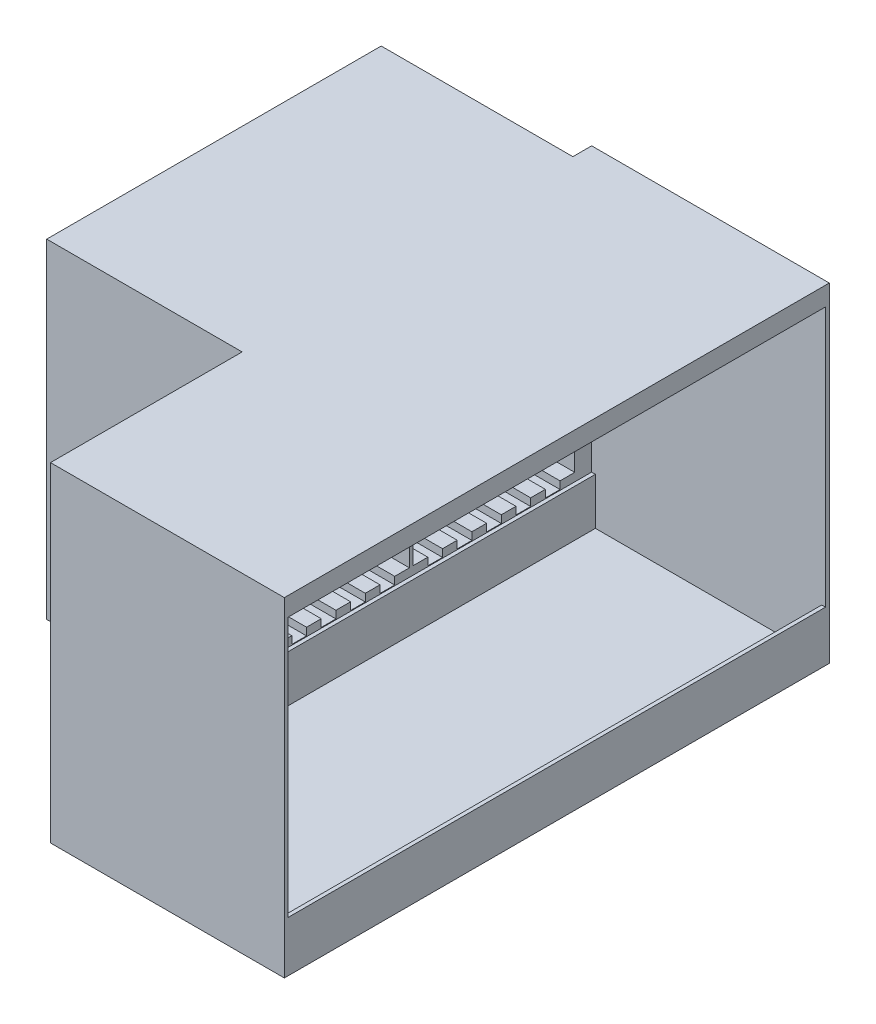
SolidWorks part; units mm, degrees
other "Исправление1"
sketch "Эскиз13" plane through (1050, -360, 1224.5) normal (0.916, -0.3443, 0.206) x (0.3981, 0.8438, -0.36)
ref_plane "Спереди" through (0, 0, 0) normal (0, 0, 1) x (1, 0, 0)
ref_plane "Сверху" through (0, 0, 0) normal (0, 1, 0) x (1, 0, 0)
ref_plane "Справа" through (0, 0, 0) normal (1, 0, 0) x (0, 0, -1)
other "Configuration Table"
sketch "Основа эскиз" plane through (0, 0, 0) normal (1, 0, 0) x (0, 0, -1)
  line L1 (-470, 438.28) -> (470, 438.28)
  line L2 (-470, 438.28) -> (-470, -438.28)
  line L3 (-470, -438.28) -> (470, -438.28)
  line L4 (470, 438.28) -> (470, -438.28)
  point P4 (0, 438.28)
  point P8 (-470, 0)
  dimension "D2" = 940
  dimension "D1" = 876.56
extrude "Основа" add sketch "Основа эскиз" along normal blind 1142.3
sketch "Вырез коретки эскиз" plane through (1142.3, 0, 0) normal (1, 0, 0) x (0, 0, -1)
  line L5 (470, 438.28) -> (-470, 438.28) construction
  line L6 (-470, 388.28) -> (460, 388.28)
  line L7 (-470, -438.28) -> (470, -438.28) construction
  line L8 (-470, 388.28) -> (-470, -303.68)
  line L9 (-470, -303.68) -> (460, -303.68)
  line L10 (460, 388.28) -> (460, -303.68)
  line L11 (-470, 438.28) -> (-470, -438.28) construction
  line L12 (470, -438.28) -> (470, 438.28) construction
  point P0 (0, 0)
  dimension "D3" = 10
  dimension "D4" = 134.6
extrude "Вырез коретки" cut sketch "Вырез коретки эскиз" against normal blind 622.3
sketch "вырез ячейки эскиз" plane through (520, 0, 0) normal (1, 0, 0) x (0, 0, -1)
  line L0 (460, 388.28) -> (-470, 388.28) construction
  line L1 (-455, 388.28) -> (-25, 388.28)
  line L2 (-455, 388.28) -> (-455, 68.28)
  line L3 (-455, 68.28) -> (-25, 68.28)
  line L4 (-25, 388.28) -> (-25, 68.28)
  line L17 (-470, 388.28) -> (-470, -303.68) construction
  dimension "D7" = 430
  dimension "D8" = 320
  dimension "D1" = 15
extrude "вырез ячейки" cut sketch "вырез ячейки эскиз" against normal blind 510
sketch "вырез двери эскиз" plane through (0, 0, 0) normal (-1, 0, 0) x (0, 0, 1)
  line L1 (25, 388.28) -> (460, 388.28)
  line L2 (25, 388.28) -> (25, 68.28)
  line L3 (25, 68.28) -> (460, 68.28)
  line L4 (460, 388.28) -> (460, 68.28)
  line L6 (455, 68.28) -> (25, 68.28) construction
  line L7 (25, 68.28) -> (25, 388.28) construction
  line L8 (455, 388.28) -> (455, 68.28) construction
  line L9 (455, 388.28) -> (455, 68.28) construction
  line L10 (25, 388.28) -> (455, 388.28) construction
  dimension "D2" = 5
extrude "вырез двери" cut sketch "вырез двери эскиз" against normal blind 10
sketch "Вырез основание низ эскиз" plane through (0, -303.68, 0) normal (0, 1, 0) x (1, 0, 0)
  line L0 (1142.3, -470) -> (1142.3, 460) construction
  line L1 (530, 460) -> (1132.3, 460)
  line L2 (530, 460) -> (530, -470)
  line L3 (530, -470) -> (1132.3, -470)
  line L4 (1132.3, 460) -> (1132.3, -470)
  line L5 (520, 460) -> (1142.3, 460) construction
  line L6 (520, -470) -> (1142.3, -470) construction
  dimension "D1" = 10
  dimension "D2" = 602.3
extrude "Вырез основание низ" cut sketch "Вырез основание низ эскиз" against normal blind 124.6
sketch "Вырез основания верх эскиз" plane through (0, 388.28, 0) normal (0, -1, 0) x (1, 0, 0)
  line L0 (520, 470) -> (1142.3, 470) construction
  line L1 (530, -460) -> (1132.3, -460)
  line L2 (530, -460) -> (530, 470)
  line L3 (530, 470) -> (1132.3, 470)
  line L4 (1132.3, -460) -> (1132.3, 470)
  line L5 (520, -460) -> (1142.3, -460) construction
  line L6 (1142.3, -460) -> (1142.3, 470) construction
  dimension "D1" = 10
  dimension "D2" = 602.3
extrude "Вырез основание верх" cut sketch "Вырез основания верх эскиз" against normal blind 40
sketch "вырез полозья эскиз" plane through (520, 0, 0) normal (1, 0, 0) x (0, 0, -1)
  line L0 (-455, 68.28) -> (-25, 68.28) construction
  line L1 (-415.9091, 68.28) -> (-376.8182, 68.28)
  line L2 (-415.9091, 68.28) -> (-415.9091, 48.28)
  line L3 (-415.9091, 48.28) -> (-376.8182, 48.28)
  line L4 (-376.8182, 68.28) -> (-376.8182, 48.28)
  dimension "D2" = 39.0909
  dimension "D3" = 39.0909
extrude "Вырез полозья" cut sketch "вырез полозья эскиз" against normal blind 510
pattern_linear "Линейный массив полозьев" count 5 spacing 78.1818 along (0, 0, -1) of "Вырез полозья"
pattern_linear "Линейный массив ячеек" count 2 spacing 440 along (0, 0, -1) count 2 spacing 350 along (0, -1, 0) of "Линейный массив полозьев", "вырез двери", "вырез ячейки"
sketch "Основание эскиз" plane through (0, 0, 470) normal (0, 0, 1) x (1, 0, 0)
  line L0 (1142.3, -438.28) -> (1142.3, -303.68)
  line L1 (1142.3, -303.68) -> (1132.3, -303.68)
  line L2 (1132.3, -303.68) -> (1132.3, -428.28)
  line L3 (1132.3, -428.28) -> (530, -428.28)
  line L4 (530, -428.28) -> (530, -303.68)
  line L5 (530, -303.68) -> (520, -303.68)
  line L6 (520, -303.68) -> (520, -438.28)
  line L7 (1142.3, -438.28) -> (0, -438.28) construction
  line L8 (520, -438.28) -> (1142.3, -438.28)
  line L9 (1132.3, 388.28) -> (1142.3, 388.28)
  line L10 (1142.3, 388.28) -> (1142.3, 438.28)
  line L11 (1142.3, 438.28) -> (520, 438.28)
  line L12 (1142.3, 438.28) -> (0, 438.28) construction
  line L13 (520, 438.28) -> (520, 388.28)
  line L14 (520, 388.28) -> (530, 388.28)
  line L15 (530, 388.28) -> (530, 428.28)
  line L16 (530, 428.28) -> (1132.3, 428.28)
  line L17 (1132.3, 428.28) -> (1132.3, 388.28)
extrude "Основание" add sketch "Основание эскиз" along normal blind 500
sketch "Стенка боквая эскиз" plane through (0, 0, 970) normal (0, 0, 1) x (1, 0, 0)
  line L1 (1142.3, 438.28) -> (520, 438.28)
  line L2 (1142.3, 438.28) -> (1142.3, -438.28)
  line L3 (1142.3, -438.28) -> (520, -438.28)
  line L4 (520, 438.28) -> (520, -438.28)
extrude "Стенка боковая" add sketch "Стенка боквая эскиз" along normal blind 10
sketch "Эскиз14" plane through (0, 0, -470) normal (0, 0, -1) x (-1, 0, 0)
  line L0 (-1142.3, 438.28) -> (0, 438.28) construction
  line L1 (0, -438.28) -> (-510, -438.28)
  line L2 (0, -438.28) -> (0, 438.28)
  line L3 (0, 438.28) -> (-510, 438.28)
  line L4 (-510, -438.28) -> (-510, 438.28)
  dimension "D1" = 510
extrude "Вырез-Вытянуть1" cut sketch "Эскиз14" against normal blind 50
equation "\"Ширина груза\"= 420"
equation "\"Глубина груза\"= 490"
equation "\"Высота груза\"= 297"
equation "\"Ширина ячейки\"= \"Ширина груза\" + 10"
equation "\"Глубина ячейки\"= \"Глубина груза\" + 10"
equation "\"Высота ячейки\"= \"Высота груза\" + 10 + 13"
equation "\"Колво ячеек ширина\"= 2"
equation "\"Колво ячеек высота\"= 2"
equation "\"Толщина стенки\"= 10"
equation "\"D2@Основа эскиз\"=( \"Ширина ячейки\" + \"Толщина стенки\" + \"Крепление дверцы\" ) * \"Колво ячеек ширина\" + \"Ширина пластины\""
equation "\"D1@Основа эскиз\"=( \"Высота ячейки\" + \"Толщина стенки\" + \"Высота пола\" ) * \"Колво ячеек высота\" + \"Отступ рейки\" * 2 + \"Высота рейки\" * 2 + \"Толщина стенки\" * 2 + \"Мотор X ширина корпуса\" + \"Мотор Y ширина корпуса\"- 8.04"
equation "\"Крепление дверцы\"= 5"
equation "\"D7@вырез ячейки эскиз\"= \"Ширина ячейки\""
equation "\"D1@вырез ячейки эскиз\" = \"Толщина стенки\" + \"Крепление дверцы\""
equation "\"D8@вырез ячейки эскиз\"= \"Высота ячейки\""
equation "\"D2@вырез двери эскиз\"= \"Крепление дверцы\""
equation "\"D1@Основа\"=\"Глубина ячейки\" + \"Глубина каретки\" + \"Толщина стенки\" * 4 + \"Ширина рейки\" "
equation "\"D1@Вырез коретки\"=\"Глубина каретки\" + \"Толщина стенки\" * 2 + \"Ширина рейки\""
equation "\"D1@Вырез основание низ эскиз\"=\"Толщина стенки\" "
equation "\"Ширина рейки\"= \"Толщина шестерни\""
equation "\"D1@вырез ячейки\"= \"Глубина ячейки\" + \"Толщина стенки\""
equation "\"D1@вырез двери\"= \"Толщина стенки\""
equation "\"D2@Вырез основание низ эскиз\"=\"Глубина каретки\" + \"Ширина рейки\""
equation "\"Высота рейки\"= 20"
equation "\"D1@Вырез основания верх эскиз\"=\"Толщина стенки\""
equation "\"D2@Вырез основания верх эскиз\"=\"Глубина каретки\" + \"Ширина рейки\" "
equation "\"D1@Вырез основание верх\" = \"Высота рейки\" + \"Отступ рейки\""
equation "\"D4@Вырез коретки эскиз\"=\"Толщина стенки\"  + \"Высота рейки\" + \"Отступ рейки\" + \"Мотор X ширина корпуса\" + \"Мотор Y ширина корпуса\""
equation "\"D1@Вырез коретки эскиз\"=\"Толщина стенки\" + \"Высота рейки\" + \"Отступ рейки\" "
equation "\"D3@Вырез коретки эскиз\" = \"Толщина стенки\""
equation "\"D1@Вырез основание низ\"=\"Мотор X ширина корпуса\" + \"Мотор Y ширина корпуса\"+\"Высота рейки\" + \"Отступ рейки\""
equation "\"Высота пола\"= 20"
equation "\"Колво полозьев\"= 5"
equation "\"D1@вырез полозья эскиз\" = \"Высота пола\""
equation "\"D2@вырез полозья эскиз\" = \"Ширина ячейки\" /  ( \"Колво полозьев\" * 2 + 1 ) "
equation "\"D3@вырез полозья эскиз\"= \"Ширина ячейки\" / ( \"Колво полозьев\" * 2 + 1 )"
equation "\"D1@Вырез полозья\" = \"Глубина ячейки\" + \"Толщина стенки\""
equation "\"D1@Линейный массив полозьев\" = \"Колво полозьев\""
equation "\"D3@Линейный массив полозьев\" = \"Ширина ячейки\" /  ( \"Колво полозьев\" * 2 + 1 )  * 2"
equation "\"D1@Линейный массив ячеек\" = \"Колво ячеек ширина\""
equation "\"D2@Линейный массив ячеек\" = \"Колво ячеек высота\""
equation "\"D3@Линейный массив ячеек\" = \"Ширина ячейки\" + \"Толщина стенки\""
equation "\"D4@Линейный массив ячеек\" = \"Высота ячейки\" + \"Высота пола\" + \"Толщина стенки\""
equation "\"Отступ рейки\"= 20"
equation "\"Глубина каретки\"= \"Глубина ячейки\" + 30 + \"Мотор Y высота корпуса\" + 20"
equation "\"D1@Стенка боковая\" = \"Толщина стенки\""
equation "\"Длинна рейки\"= ( \"Ширина ячейки\" + \"Толщина стенки\" + \"Крепление дверцы\" ) * \"Колво ячеек ширина\" + \"Ширина ячейки выгрузки\" * \"Колво выгрузки\" + \"Толщина стенки\""
equation "\"D1@Основание\" = \"Длинна рейки\" -  ( \"Ширина ячейки\" + \"Толщина стенки\" + \"Крепление дверцы\" )  * \"Колво ячеек ширина\" - \"Толщина стенки\""
equation "\"Отступ шпильки\"= 20"
equation "\"Диаметр шпильки\"= 5"
equation "\"Длинна шпильки\"= ( \"Высота ячейки\" + \"Толщина стенки\" + \"Высота пола\" ) * \"Колво ячеек высота\" + ( \"Толщина стенки\" + \"Отступ рейки\" ) * 2 "
equation "\"Ширина пластины\"= 50  "
equation "\"Высота зона выгрузки\"= \"Высота ячейки\" * 2 + \"Толщина стенки\" * 2"
equation "\"Колво выгрузки\"= 1"
equation "\"D1@Эскиз14\"= \"Толщина стенки\" + \"Глубина ячейки\""
equation "\"D1@Вырез-Вытянуть1\"= \"Ширина пластины\""
equation "\"Ширина ячейки выгрузки\"= \"Ширина ячейки\" + \"Толщина стенки\" + \"Отступ крепления мотора фиксации\"*2"
equation "\"Отступ крепления мотора фиксации\" = 30"
equation "\"Мотор X ширина корпуса\"= 42.3"
equation "\"Мотор X высота корпуса\"= 42.3"
equation "\"Мотор X длина корпуса\"= 40"
equation "\"Мотор X вылет вала\"= 19.8"
equation "\"Мотор Y ширина корпуса\"= 42.3"
equation "\"Мотор Y высота корпуса\"= 42.3"
equation "\"Мотор Y длина корпуса\"= 48"
equation "\"Мотор Y вылет вала\"= 30"
equation "\"Мотор Z ширина корпуса\"= 42"
equation "\"Мотор Z высота корпуса\"= 42"
equation "\"Мотор Z длина корпуса\"= 40"
equation "\"Мотор Z вылет вала\"= 23"
equation "\"Мотор диаметр вала ПРЕДВ\"= 5"
equation "\"Мотор шаг крепления ПРЕДВ\"= 31"
equation "\"Мотор диаметр отверстий ПРЕДВ\"= 3"
equation "\"Мотор глубина отверстий ПРЕДВ\"= 4.5"
equation "\"Мотор диаметр буртика ПРЕДВ\"= 22"
equation "\"Мотор высота буртика ПРЕДВ\"= 2"
equation "\"Мотор диаметр шкива ПРЕДВ\"= 16"
equation "\"Мотор длина шкива ПРЕДВ\"= 12"
equation "\"Мотор отступ шкива ПРЕДВ\"= 5"
equation "\"Мотор X шаг градусов\"= 1.8"
equation "\"Мотор Y шаг градусов\"= 1.8"
equation "\"Мотор Z шаг градусов\"= 1.8"
equation "\"Мотор Y диаметр ротора\"= 25.78"
equation "\"Толщина шестерни\"= 10"
